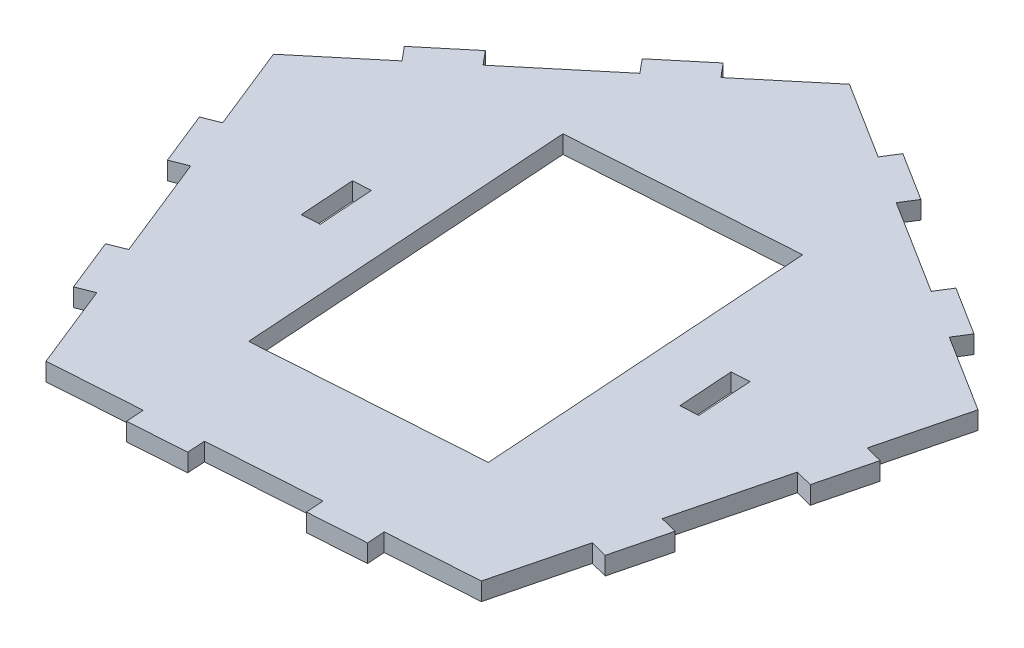
SolidWorks part; units mm, degrees
ref_plane "Front Plane" through (0, 0, 0) normal (0, 0, 1) x (1, 0, 0)
ref_plane "Top Plane" through (0, 0, 0) normal (0, 1, 0) x (1, 0, 0)
ref_plane "Right Plane" through (0, 0, 0) normal (1, 0, 0) x (0, 0, -1)
sketch "Sketch1" plane through (0, 0, 0) normal (0, 1, 0) x (1, 0, 0)
  line L1 (-59.9258, 15.1181) -> (-32.8962, -52.3211)
  line L2 (-32.8962, -52.3211) -> (39.5948, -47.4543)
  line L3 (39.5948, -47.4543) -> (57.3672, 22.9927)
  line L4 (57.3672, 22.9927) -> (-4.14, 61.6646)
  line L5 (-4.14, 61.6646) -> (-59.9258, 15.1181)
  circle A0 centre (0, 0) radius 50 construction
  dimension "D1" = 100
extrude "Boss-Extrude1" add sketch "Sketch1" along normal blind 3.18
ref_axis "Axis" through (0, 3.339, 0) along (0, -1, 0)
sketch "Axis Check" plane through (0, 3.18, 0) normal (0, 1, 0) x (1, 0, 0)
  line L0 (3.3493, -49.8877) -> (-4.14, 61.6646) construction
  line L1 (-32.8962, -52.3211) -> (39.5948, -47.4543) construction
  line L2 (57.3672, 22.9927) -> (-46.411, -18.6015) construction
  line L3 (-59.9258, 15.1181) -> (-32.8962, -52.3211) construction
  line L4 (-32.0329, 38.3913) -> (39.5948, -47.4543) construction
  line L5 (-4.14, 61.6646) -> (-59.9258, 15.1181) construction
  line L6 (-59.9258, 15.1181) -> (48.481, -12.2308) construction
  line L7 (39.5948, -47.4543) -> (57.3672, 22.9927) construction
  line L8 (-32.8962, -52.3211) -> (26.6136, 42.3287) construction
  line L9 (57.3672, 22.9927) -> (-4.14, 61.6646) construction
sketch "Sketch2" plane through (0, 0, 0) normal (0, -1, 0) x (1, 0, 0)
  line L0 (-53.8107, 0.1392) -> (-50.859, -1.0438)
  line L1 (-53.8107, 0.1392) -> (-50.1723, 9.2172)
  line L2 (-50.859, -1.0438) -> (-47.2205, 8.0342)
  line L3 (-50.1723, 9.2172) -> (-47.2205, 8.0342)
  line L4 (-59.9258, -15.1181) -> (-32.8962, 52.3211) construction
  line L5 (-42.6498, 27.9858) -> (-39.0113, 37.0638)
  line L6 (-42.6498, 27.9858) -> (-39.6981, 26.8028)
  line L7 (-39.0113, 37.0638) -> (-36.0596, 35.8808)
  line L8 (-39.6981, 26.8028) -> (-36.0596, 35.8808)
  line L9 (-46.411, 18.6015) -> (-19.2439, 7.7129) construction
  line L10 (-40.8306, 32.5248) -> (-37.8788, 31.3418) construction
  dimension "D1" = 3.18
  dimension "D2" = 9.78
  dimension "D3" = 10.11
extrude "Cut F" [suppressed] cut sketch "Sketch2" against normal through all
sketch "Sketch4" [suppressed] plane through (0, 3.18, 0) normal (0, 1, 0) x (1, 0, 0)
  line L9 (26.6136, 42.3287) -> (-26.6136, -42.3287) construction
  line L10 (57.3672, 22.9927) -> (-4.14, 61.6646) construction
  line L11 (-27.7286, -6.3206) -> (-6.3206, 27.7286)
  line L12 (-27.7286, -6.3206) -> (6.3206, -27.7286)
  line L13 (-6.3206, 27.7286) -> (27.7286, 6.3206)
  line L14 (6.3206, -27.7286) -> (27.7286, 6.3206)
  line L15 (-27.7286, -6.3206) -> (27.7286, 6.3206) construction
  line L16 (-6.3206, 27.7286) -> (6.3206, -27.7286) construction
  line L20 (0, 0) -> (39.0006, -24.5211) construction
  circle A0 centre (-14.9622, -23.7972) radius 3.25
  circle A1 centre (23.7972, -14.9622) radius 3.25
  point P5 (0, 0)
  point P6 (-14.9622, -23.7972)
  dimension "D3" = 6.5
  dimension "D1" = 40.22
  dimension "D2" = 40.22
  dimension "D4" = 8
  dimension "D5" = 8
extrude "Top Cut" [suppressed] cut sketch "Sketch4" against normal blind 10
sketch "Sketch7" [suppressed] plane through (0, 3.18, 0) normal (0, 1, 0) x (1, 0, 0)
  line L0 (0, 0) -> (26.6136, 42.3287) construction
  line L1 (57.3672, 22.9927) -> (-4.14, 61.6646) construction
  line L2 (1.0645, 1.6931) -> (-22.7326, 16.6553) construction
  line L3 (-6.1086, 1.4782) -> (-24.8617, 13.269) construction
  line L5 (-6.3206, 27.7286) -> (-27.7286, -6.3206) construction
  circle A0 centre (-22.7326, 16.6553) radius 1
  circle A1 centre (-24.8617, 13.269) radius 1
  dimension "D5" = 2
  dimension "D1" = 4
  dimension "D2" = 2
  dimension "D3" = 8
  dimension "D4" = 8
extrude "Top Cut 2" [suppressed] cut sketch "Sketch7" against normal through all
sketch "Sketch8" plane through (0, 3.18, 0) normal (0, 1, 0) x (1, 0, 0)
  line L0 (3.3493, -49.8877) -> (-4.14, 61.6646) construction
  line L5 (-32.8962, -52.3211) -> (39.5948, -47.4543) construction
  line L6 (-17.9455, -31.2723) -> (21.9647, -28.5929)
  line L11 (-17.9455, -31.2723) -> (-21.9647, 28.5929)
  line L12 (21.9647, -28.5929) -> (17.9455, 31.2723)
  line L13 (-21.9647, 28.5929) -> (17.9455, 31.2723)
  point P4 (1.4955, -22.2759)
  dimension "D1" = 60
  dimension "D2" = 40
  dimension "D3" = 20
extrude "Bottom Cut" cut sketch "Sketch8" against normal blind 10
sketch "Sketch9" plane through (0, 3.18, 0) normal (0, 1, 0) x (1, 0, 0)
  line L0 (19.9551, 1.3397) -> (-19.9551, -1.3397) construction
  line L1 (21.9647, -28.5929) -> (17.9455, 31.2723) construction
  line L2 (-21.9647, 28.5929) -> (-17.9455, -31.2723) construction
  line L3 (-19.9551, -1.3397) -> (-44.4689, -2.9855) construction
  line L4 (19.9551, 1.3397) -> (43.083, 2.8925) construction
  line L5 (-32.8962, -52.3211) -> (39.5948, -47.4543) construction
  line L6 (-29.6051, -6.8886) -> (-32.7779, -7.1016)
  line L7 (-29.6051, -6.8886) -> (-30.2602, 2.8694)
  line L8 (-30.2602, 2.8694) -> (-33.433, 2.6564)
  line L9 (-32.7779, -7.1016) -> (-33.433, 2.6564)
  line L10 (-29.6051, -6.8886) -> (-33.433, 2.6564) construction
  line L11 (-30.2602, 2.8694) -> (-32.7779, -7.1016) construction
  line L12 (33.433, -2.6564) -> (30.2602, -2.8694)
  line L13 (33.433, -2.6564) -> (32.7779, 7.1016)
  line L14 (32.7779, 7.1016) -> (29.6051, 6.8886)
  line L15 (30.2602, -2.8694) -> (29.6051, 6.8886)
  line L16 (33.433, -2.6564) -> (29.6051, 6.8886) construction
  line L17 (32.7779, 7.1016) -> (30.2602, -2.8694) construction
  line L18 (-32.8962, -52.3211) -> (39.5948, -47.4543) construction
  point P6 (-31.519, -2.1161)
  point P13 (31.519, 2.1161)
  dimension "D1" = 9.78
  dimension "D2" = 3.18
  dimension "D3" = 3.18
  dimension "D4" = 9.78
  dimension "D5" = 10
  dimension "D6" = 10
extrude "Battery Holder Cut" cut sketch "Sketch9" against normal blind 3.18
sketch "Sketch3" plane through (0, 3.18, 0) normal (0, 1, 0) x (1, 0, 0)
  line L0 (0, 0) -> (-40.9819, 49.1167) construction
  line L1 (-49.5112, 27.9494) -> (-45.4366, 23.066)
  line L3 (-45.4366, 23.066) -> (-37.5894, 29.6135)
  line L4 (-41.664, 34.4969) -> (-37.5894, 29.6135)
  line L5 (-4.14, 61.6646) -> (-59.9258, 15.1181) construction
  line L6 (-71.9961, 5.0469) -> (-69.9588, 2.6052)
  line L7 (-71.9961, 5.0469) -> (-47.4739, 25.5077)
  line L14 (-26.4764, 47.1691) -> (-22.4018, 42.2857)
  line L16 (-22.4018, 42.2857) -> (-14.5546, 48.8333)
  line L17 (-18.6292, 53.7166) -> (-14.5546, 48.8333)
  line L18 (-42.539, 27.5695) -> (-41.513, 26.3398) construction
  line L19 (-49.5112, 27.9494) -> (-41.664, 34.4969)
  line L21 (-26.4764, 47.1691) -> (-18.6292, 53.7166)
  line L22 (-16.5919, 51.275) -> (4.7866, 69.1127)
  line L23 (-39.6267, 32.0552) -> (-24.4391, 44.7274)
  line M18 (-4.14, 61.6646) -> (-59.9258, 15.1181)
  dimension "D1" = 3.18
  dimension "D2" = 10.22
  dimension "D3" = 9.89
  dimension "D4" = 100
extrude "Extrude M" add sketch "Sketch3" against normal up to surface (3.18 mm away) contours L21 L14 L7 L17 | L19 L1 L4 M18 region at (-44.5689, 3.18, -30.0023) region at (-21.5341, 3.18, -49.222) up to face at (-31.519, 0, 2.1161)
pattern_circular "Circle F" [suppressed] count 5 over 360 about axis through (0, 3.339, 0) along (0, -1, 0) of bodies 173
pattern_circular "Circle M" count 5 over 360 about axis through (0, 3.339, 0) along (0, -1, 0) of "Extrude M"
pattern_circular "Circle Side F" [suppressed] count 5 over 360 about axis through (0, 3.339, 0) along (0, -1, 0) of bodies 173
pattern_circular "Circle Side M" [suppressed] count 5 over 360 about axis through (0, 3.339, 0) along (0, -1, 0) of bodies 168
equation "\"kerf\"= .22mm"
equation "\"tabWidthF\"= 10 - \"kerf\""
equation "\"tabThickness\"= 3.18"
equation "\"D1@Sketch2\"=\"tabThickness\""
equation "\"tabWidthM\"= 10 + \"kerf\""
equation "\"halfkerf\"= \"kerf\" / 2.00mm"
equation "\"D1@Sketch9\"=\"tabWidthF\""
equation "\"D2@Sketch9\"=\"tabThickness\""
equation "\"D3@Sketch9\"=\"tabThickness\""
equation "\"D4@Sketch9\"=\"tabWidthF\""
equation "\"D1@Battery Holder Cut\"=\"tabThickness\""
equation "\"tabLength\" = \"kerf\" + 12"
